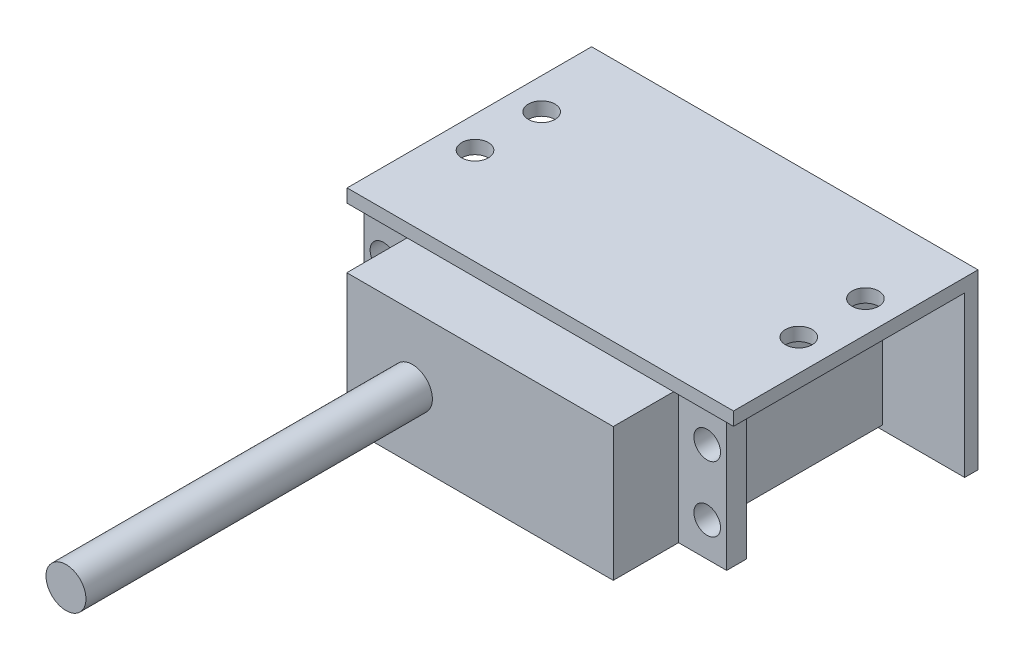
SolidWorks part; units mm, degrees
ref_plane "Front Plane" through (0, 0, 0) normal (0, 0, 1) x (1, 0, 0)
ref_plane "Top Plane" through (0, 0, 0) normal (0, 1, 0) x (1, 0, 0)
ref_plane "Right Plane" through (0, 0, 0) normal (1, 0, 0) x (0, 0, -1)
sketch "Sketch2" plane through (0, 0, 0) normal (0, 0, 1) x (1, 0, 0)
  line L0 (-24.3, 4.9) -> (-24.3, -4.9) construction
  line L1 (-27.22, 10) -> (27.22, 10)
  line L2 (-27.22, 10) -> (-27.22, -10)
  line L3 (-27.22, -10) -> (27.22, -10)
  line L4 (27.22, 10) -> (27.22, -10)
  line L5 (-27.22, 10) -> (27.22, -10) construction
  line L6 (-27.22, -10) -> (27.22, 10) construction
  line L7 (-24.3, -4.9) -> (24.3, -4.9) construction
  line L8 (24.3, -4.9) -> (24.3, 4.9) construction
  line L9 (24.3, 4.9) -> (-24.3, 4.9) construction
  line L10 (0, 10) -> (0, 4.9) construction
  line L11 (-27.22, 0) -> (-24.3, 0) construction
  line L13 (-20, 10) -> (20, 10)
  line L14 (-20, 10) -> (-20, -10)
  line L15 (-20, -10) -> (20, -10)
  line L16 (20, 10) -> (20, -10)
  line L17 (-20, 10) -> (20, -10) construction
  line L18 (-20, -10) -> (20, 10) construction
  circle A0 centre (-24.3, 4.9) radius 2
  circle A1 centre (-24.3, -4.9) radius 2
  circle A2 centre (24.3, 4.9) radius 2
  circle A3 centre (24.3, -4.9) radius 2
  circle A4 centre (-10.15, 0) radius 7
  circle A5 centre (-10.15, 0) radius 3
  point P0 (0, 0)
  point P18 (0, 0)
  dimension "D5" = 4
  dimension "D8" = 6
  dimension "D9" = 14
  dimension "D1" = 54.44
  dimension "D2" = 20
  dimension "D3" = 9.8
  dimension "D4" = 48.6
  dimension "D6" = 34.45
  dimension "D7" = 40
extrude "Boss-Extrude1" add sketch "Sketch2" against normal blind 40.45 contours L16 L1 L14 L3 A4 | A4 | A5 region at (2.4185, 0, 0) region at (-16.952, 0, 0) region at (-10.15, 0, 0)
extrude "Boss-Extrude2" add sketch "Sketch2<3>" along normal blind 3 from offset 12.8 contours L14 L1 L2 L3 A1 A0 | L1 L16 L3 L4 A3 A2 region at (-23.4646, 0, 0) region at (23.4646, 0, 0) offset against normal yes
sketch "Sketch2<3>" plane through (0, 0, 0) normal (0, 0, 1) x (1, 0, 0) same geometry as "Sketch2"
extrude "Boss-Extrude3" add sketch "Sketch2<4>" along normal blind 52 contours A5
sketch "Sketch2<4>" plane through (0, 0, 0) normal (0, 0, 1) x (1, 0, 0) same geometry as "Sketch2"
sketch "Sketch3" plane through (0, 10, 0) normal (0, 1, 0) x (1, 0, 0)
  line L1 (-29, 45.75) -> (29, 45.75)
  line L2 (-29, 45.75) -> (-29, 9.05)
  line L3 (-29, 9.05) -> (29, 9.05)
  line L4 (29, 45.75) -> (29, 9.05)
  line L5 (-29, 45.75) -> (29, 9.05) construction
  line L6 (-29, 9.05) -> (29, 45.75) construction
  line L8 (-27.22, 9.8) -> (-20, 9.8) construction
  line L9 (-24.3, 33.55) -> (24.3, 33.55) construction
  line L10 (24.3, 33.55) -> (24.3, 23.55) construction
  line L11 (24.3, 23.55) -> (-24.3, 23.55) construction
  line L12 (-24.3, 23.55) -> (-24.3, 33.55) construction
  circle A0 centre (-24.3, 33.55) radius 2
  circle A1 centre (-24.3, 23.55) radius 2
  circle A2 centre (24.3, 33.55) radius 2
  circle A3 centre (24.3, 23.55) radius 2
  point P0 (0, 27.4)
  point P16 (0, 33.55)
  dimension "D6" = 4
  dimension "D1" = 58
  dimension "D2" = 36.7
  dimension "D3" = 0.75
  dimension "D4" = 14.5
  dimension "D5" = 10
  dimension "D7" = 48.6
extrude "Boss-Extrude4" add sketch "Sketch3" along normal blind 2
sketch "Sketch4" plane through (0, 10, 0) normal (0, -1, 0) x (1, 0, 0)
  line L0 (29, -9.05) -> (29, -45.75) construction
  line L1 (-29, -45.75) -> (29, -45.75)
  line L2 (-29, -45.75) -> (-29, -43.75)
  line L3 (-29, -43.75) -> (29, -43.75)
  line L4 (29, -45.75) -> (29, -43.75)
  dimension "D1" = 2
extrude "Boss-Extrude5" add sketch "Sketch4" along normal blind 24
ref_plane "Plane1" through (0, 0, 0) normal (0, 1, 0) x (1, 0, 0)
